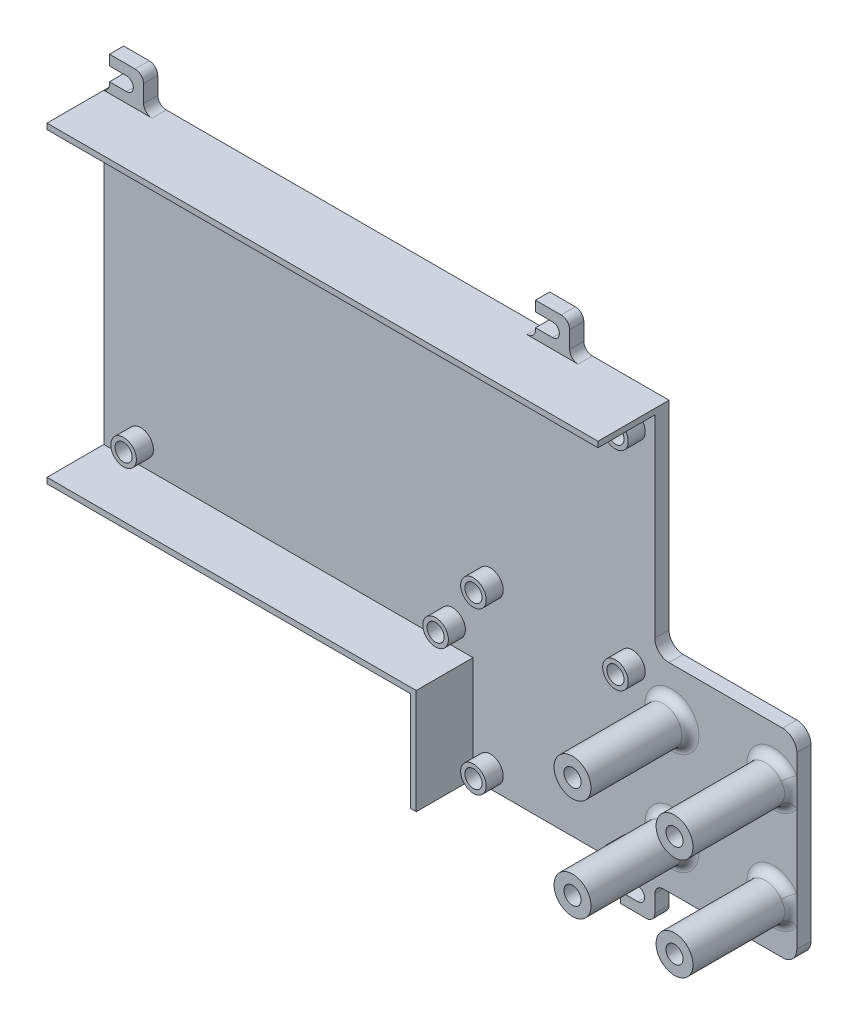
SolidWorks part; units mm, degrees
material "ABS"
ref_plane "X-Y Datum" through (0, 0, 0) normal (0, 0, 1) x (1, 0, 0)
ref_plane "X-Z Datum" through (0, 0, 0) normal (0, 1, 0) x (1, 0, 0)
ref_plane "Y-Z Datum" through (0, 0, 0) normal (1, 0, 0) x (0, 0, -1)
sketch "Sketch1" plane through (0, 0, 0) normal (0, 0, 1) x (1, 0, 0)
  line L1 (-167.3248, 270.3744) -> (-39.3248, 270.3744)
  line L2 (-167.3248, 270.3744) -> (-167.3248, 160.3744)
  line L3 (-167.3248, 160.3744) -> (-39.3248, 160.3744)
  line L4 (-39.3248, 270.3744) -> (-39.3248, 160.3744)
  line L5 (-39.3248, 270.3744) -> (26.6752, 270.3744)
  line L6 (-39.3248, 270.3744) -> (-39.3248, 125.3744)
  line L7 (-39.3248, 125.3744) -> (26.6752, 125.3744)
  line L8 (26.6752, 270.3744) -> (26.6752, 125.3744)
  line L9 (26.6752, 125.3744) -> (76.6752, 125.3744)
  line L10 (26.6752, 125.3744) -> (26.6752, 195.3744)
  line L11 (26.6752, 195.3744) -> (76.6752, 195.3744)
  line L12 (76.6752, 125.3744) -> (76.6752, 195.3744)
  dimension "D1" = 110
  dimension "D2" = 128
  dimension "D3" = 66
  dimension "D4" = 145
  dimension "D5" = 50
  dimension "D6" = 70
extrude "Boss-Extrude1" add sketch "Sketch1" along normal blind 5 contours L4 L1 L2 L3 | L8 L5 L4 L6 L7 | L9 L12 L11 L8 region at (-103.3248, 215.3744, 0) region at (-6.3248, 197.8744, 0) region at (51.6752, 160.3744, 0)
sketch "Sketch2" plane through (0, 0, 5) normal (0, 0, 1) x (1, 0, 0)
  circle A0 centre (-44.4998, 262.4914) radius 3.025
  circle A1 centre (-154.3548, 262.4914) radius 3.025
  circle A2 centre (-154.3548, 262.4914) radius 4.5
  circle A3 centre (-44.4998, 262.4914) radius 4.5
  circle A4 centre (-44.4998, 169.5274) radius 3.025
  circle A5 centre (-44.4998, 169.5274) radius 4.5
  circle A6 centre (-154.3548, 169.5274) radius 4.5
  circle A7 centre (-154.3548, 169.5274) radius 3.025
  circle A8 centre (-31.1818, 131.5554) radius 4.5
  circle A9 centre (-31.1818, 131.5554) radius 3.025
  circle A10 centre (18.8182, 131.5554) radius 3.025
  circle A11 centre (18.8182, 131.5554) radius 4.5
  circle A12 centre (18.8182, 188.3054) radius 3.025
  circle A13 centre (18.8182, 188.3054) radius 4.5
  circle A14 centre (-31.1818, 188.3054) radius 4.5
  circle A15 centre (-31.1818, 188.3054) radius 3.025
  circle A16 centre (-31.1818, 261.5554) radius 3.025
  circle A17 centre (-31.1818, 261.5554) radius 4.5
  circle A18 centre (18.8182, 261.5554) radius 4.5
  circle A19 centre (18.8182, 261.5554) radius 3.025
  point P0 (-154.3548, 262.4914)
  point P1 (-44.4998, 262.4914)
  point P3 (-44.4998, 169.5274)
  point P5 (-154.3548, 169.5274)
  point P7 (18.8182, 261.5554)
  point P9 (-31.1818, 261.5554)
  point P11 (-31.1818, 188.3054)
  point P13 (-31.1818, 131.5554)
  point P15 (18.8182, 131.5554)
  point P17 (18.8182, 188.3054)
  dimension "D1" = 6.05
  dimension "D2" = 9
extrude "Boss-Extrude2" add sketch "Sketch2" along normal blind 6
sketch "Sketch3" plane through (0, 0, 5) normal (0, 0, 1) x (1, 0, 0)
  line L0 (26.6752, 270.3744) -> (26.6752, 195.3744) construction
  line L1 (-167.3248, 270.3744) -> (26.6752, 270.3744)
  line L2 (-167.3248, 270.3744) -> (-167.3248, 268.3744)
  line L3 (-167.3248, 268.3744) -> (26.6752, 268.3744)
  line L4 (26.6752, 270.3744) -> (26.6752, 268.3744)
  line L6 (-167.3248, 160.3744) -> (-39.3248, 160.3744)
  line L7 (-167.3248, 160.3744) -> (-167.3248, 162.3744)
  line L8 (-167.3248, 162.3744) -> (-39.3248, 162.3744)
  line L9 (-39.3248, 160.3744) -> (-39.3248, 162.3744)
  line L10 (-39.3248, 125.3744) -> (-37.3248, 125.3744)
  line L11 (-39.3248, 125.3744) -> (-39.3248, 162.3744)
  line L12 (-39.3248, 162.3744) -> (-37.3248, 162.3744)
  line L13 (-37.3248, 125.3744) -> (-37.3248, 162.3744)
  line M14 (-167.3248, 160.3744) -> (-39.3248, 160.3744)
  line M15 (-39.3248, 160.3744) -> (-39.3248, 125.3744)
  line M16 (-39.3248, 125.3744) -> (76.6752, 125.3744)
  line M19 (26.6752, 195.3744) -> (26.6752, 270.3744)
  line M20 (26.6752, 270.3744) -> (-167.3248, 270.3744)
  line M21 (-167.3248, 270.3744) -> (-167.3248, 160.3744)
  dimension "D1" = 2
  dimension "D2" = 2
  dimension "D3" = 2
extrude "Boss-Extrude3" add sketch "Sketch3" along normal blind 20 contours L13 L12 L9 M16 M15 | L9 L8 M14 M21 | L3 M21 M19 M20 region at (-103.3248, 161.3744, 5) region at (-70.3248, 269.3744, 5) region at (-38.3248, 143.8744, 5)
sketch "Sketch5" plane through (0, 0, 5) normal (0, 0, 1) x (1, 0, 0)
  circle A0 centre (32.6993, 178.3575) radius 3.025
  circle A1 centre (68.6203, 178.3575) radius 3.025
  circle A2 centre (68.6203, 142.4365) radius 3.025
  circle A3 centre (32.6993, 142.4365) radius 3.025
  circle A4 centre (68.6203, 178.3575) radius 6.5
  circle A5 centre (32.6993, 178.3575) radius 6.5
  circle A6 centre (32.6993, 142.4365) radius 6.5
  circle A7 centre (68.6203, 142.4365) radius 6.5
  point P1 (32.6993, 178.3575)
  point P3 (32.6993, 142.4365)
  dimension "D1" = 6.05
  dimension "D2" = 13
extrude "Boss-Extrude4" add sketch "Sketch5" along normal blind 35
fillet "Fillet1" radius 3 4 edges at (39.1993, 178.3575, 5) (75.1203, 178.3575, 5) (75.1203, 142.4365, 5) (39.1993, 142.4365, 5)
sketch "Sketch6" plane through (0, 0, 0) normal (0, 0, -1) x (-1, 0, 0)
  line L0 (167.3248, 160.3744) -> (39.3248, 160.3744) construction
  line L1 (102.3248, 160.3744) -> (90.3248, 160.3744)
  line L2 (102.3248, 160.3744) -> (102.3248, 148.3744)
  line L3 (102.3248, 148.3744) -> (90.3248, 148.3744)
  line L4 (90.3248, 160.3744) -> (90.3248, 148.3744)
  line L5 (-26.6752, 270.3744) -> (167.3248, 270.3744) construction
  line L6 (165.3248, 270.3744) -> (153.3248, 270.3744)
  line L7 (165.3248, 270.3744) -> (165.3248, 282.3744)
  line L8 (165.3248, 282.3744) -> (153.3248, 282.3744)
  line L9 (153.3248, 270.3744) -> (153.3248, 282.3744)
  line L10 (37.3248, 125.3744) -> (-76.6752, 125.3744) construction
  line L11 (-14.6752, 125.3744) -> (-26.6752, 125.3744)
  line L12 (-14.6752, 125.3744) -> (-14.6752, 113.3744)
  line L13 (-14.6752, 113.3744) -> (-26.6752, 113.3744)
  line L14 (-26.6752, 125.3744) -> (-26.6752, 113.3744)
  line L15 (96.3248, 160.3744) -> (96.3248, 148.3744) construction
  line L16 (15.3248, 270.3744) -> (3.3248, 270.3744)
  line L17 (15.3248, 270.3744) -> (15.3248, 282.3744)
  line L18 (15.3248, 282.3744) -> (3.3248, 282.3744)
  line L19 (3.3248, 270.3744) -> (3.3248, 282.3744)
  line L20 (167.3248, 162.3744) -> (167.3248, 160.3744) construction
  line L21 (159.3248, 282.3744) -> (159.3248, 270.3744) construction
  line L22 (9.3248, 282.3744) -> (9.3248, 270.3744) construction
  line L23 (-20.6752, 125.3744) -> (-20.6752, 113.3744) construction
  line L24 (167.3248, 268.3744) -> (167.3248, 162.3744) construction
  line L27 (-26.6752, 268.3744) -> (-26.6752, 195.3744) construction
  line L28 (-76.6752, 125.3744) -> (-76.6752, 137.3997) construction
  circle A0 centre (96.3248, 154.3744) radius 2 construction
  circle A1 centre (-20.6752, 119.3744) radius 2 construction
  circle A2 centre (9.3248, 276.3744) radius 2 construction
  circle A3 centre (159.3248, 276.3744) radius 2 construction
  dimension "D1" = 4
  dimension "D2" = 12
  dimension "D3" = 12
  dimension "D4" = 65
  dimension "D5" = 2
  dimension "D6" = 30
  dimension "D7" = 50
extrude "Boss-Extrude5" add sketch "Sketch6" against normal blind 5
hole_wizard "M4 Clearance Hole1" positions "Sketch9" profile "Sketch8" hole size "M4" standard "ANSI Metric" end condition through all
sketch "Sketch9" plane through (0, 0, 5) normal (0, 0, 1) x (1, 0, 0)
  line L0 (-96.3248, 160.3744) -> (-96.3248, 148.3744) construction
  point P0 (-96.3248, 154.3744)
  point P4 (-159.3248, 276.3744)
  point P7 (-9.3248, 276.3744)
  point P10 (20.6752, 119.3744)
sketch "Sketch8" plane through (-96.3248, 154.3744, 5) normal (1, 0, 0) x (0, -1, 0)
  line L0 (0, 0) -> (0, 5)
  line L1 (0, 5) -> (2.4, 5)
  line L2 (2.4, 5) -> (2.4, 0)
  line L5 (2.4, 0) -> (0, 0)
  line L11 (0, -6.35) -> (0, 107.95) construction
  dimension "Thru Hole Dia." = 4.8
  dimension "Thru Hole Depth" = 5
sketch "Sketch10" plane through (0, 0, 5) normal (0, 0, 1) x (1, 0, 0)
  line L0 (-159.3248, 278.7744) -> (-165.3248, 278.7744)
  line L1 (-159.3248, 282.3744) -> (-159.3248, 270.3744) construction
  line L2 (-165.3248, 270.3744) -> (-165.3248, 282.3744) construction
  line L3 (-159.3248, 273.9744) -> (-165.3248, 273.9744)
  line L4 (-96.3248, 156.7744) -> (-102.3248, 156.7744)
  line L5 (-96.3248, 160.3744) -> (-96.3248, 148.3744) construction
  line L6 (-102.3248, 160.3744) -> (-102.3248, 148.3744) construction
  line L7 (-96.3248, 151.9744) -> (-102.3248, 151.9744)
  line L8 (20.6752, 121.7744) -> (14.6752, 121.7744)
  line L9 (20.6752, 125.3744) -> (20.6752, 113.3744) construction
  line L10 (14.6752, 125.3744) -> (14.6752, 113.3744) construction
  line L11 (20.6752, 116.9744) -> (14.6752, 116.9744)
  line L12 (-9.3248, 278.7744) -> (-15.3248, 278.7744)
  line L13 (-9.3248, 282.3744) -> (-9.3248, 270.3744) construction
  line L14 (-15.3248, 270.3744) -> (-15.3248, 282.3744) construction
  line L15 (-9.3248, 273.9744) -> (-15.3248, 273.9744)
  line L20 (-102.3248, 160.3744) -> (-102.3248, 148.3744)
  line L21 (-102.3248, 148.3744) -> (-90.3248, 148.3744)
  line L22 (-90.3248, 148.3744) -> (-90.3248, 160.3744)
  line L23 (-90.3248, 160.3744) -> (-102.3248, 160.3744)
  line L24 (-102.3248, 160.3744) -> (-102.3248, 148.3744)
  line L25 (-102.3248, 148.3744) -> (-90.3248, 148.3744)
  line L26 (-90.3248, 148.3744) -> (-90.3248, 160.3744)
  line L27 (-90.3248, 160.3744) -> (-102.3248, 160.3744)
  line L28 (-15.3248, 282.3744) -> (-15.3248, 270.3744)
  line L29 (-15.3248, 270.3744) -> (-3.3248, 270.3744)
  line L30 (76.6752, 147.4732) -> (76.6752, 173.3208)
  line L31 (76.6752, 183.3942) -> (76.6752, 195.3744)
  line L32 (76.6752, 195.3744) -> (26.6752, 195.3744)
  line L33 (26.6752, 195.3744) -> (26.6752, 268.3744)
  line L34 (26.6752, 268.3744) -> (-167.3248, 268.3744)
  line L35 (-167.3248, 268.3744) -> (-167.3248, 162.3744)
  line L36 (-167.3248, 162.3744) -> (-37.3248, 162.3744)
  line L37 (-37.3248, 162.3744) -> (-37.3248, 125.3744)
  line L38 (-37.3248, 125.3744) -> (14.6752, 125.3744)
  line L39 (14.6752, 125.3744) -> (14.6752, 113.3744)
  line L40 (14.6752, 113.3744) -> (26.6752, 113.3744)
  line L41 (26.6752, 113.3744) -> (26.6752, 125.3744)
  line L44 (76.6752, 147.4732) -> (76.6752, 173.3208)
  line L45 (76.6752, 183.3942) -> (76.6752, 195.3744)
  line L46 (76.6752, 195.3744) -> (26.6752, 195.3744)
  line L47 (26.6752, 195.3744) -> (26.6752, 268.3744)
  line L48 (26.6752, 268.3744) -> (-167.3248, 268.3744)
  line L49 (-167.3248, 268.3744) -> (-167.3248, 162.3744)
  line L50 (-167.3248, 162.3744) -> (-37.3248, 162.3744)
  line L51 (-37.3248, 162.3744) -> (-37.3248, 125.3744)
  line L52 (-37.3248, 125.3744) -> (14.6752, 125.3744)
  line L53 (14.6752, 125.3744) -> (14.6752, 113.3744)
  line L54 (14.6752, 113.3744) -> (26.6752, 113.3744)
  line L55 (26.6752, 113.3744) -> (26.6752, 125.3744)
  line L58 (-3.3248, 270.3744) -> (-3.3248, 282.3744)
  line L59 (-3.3248, 282.3744) -> (-15.3248, 282.3744)
  line L60 (-15.3248, 282.3744) -> (-15.3248, 270.3744)
  line L61 (-15.3248, 270.3744) -> (-3.3248, 270.3744)
  line L62 (-3.3248, 270.3744) -> (-3.3248, 282.3744)
  line L63 (-3.3248, 282.3744) -> (-15.3248, 282.3744)
  line L64 (-165.3248, 282.3744) -> (-165.3248, 270.3744)
  line L65 (-165.3248, 270.3744) -> (-153.3248, 270.3744)
  line L66 (-153.3248, 270.3744) -> (-153.3248, 282.3744)
  line L67 (-153.3248, 282.3744) -> (-165.3248, 282.3744)
  line L68 (-165.3248, 282.3744) -> (-165.3248, 270.3744)
  line L69 (-165.3248, 270.3744) -> (-153.3248, 270.3744)
  line L70 (-153.3248, 270.3744) -> (-153.3248, 282.3744)
  line L71 (-153.3248, 282.3744) -> (-165.3248, 282.3744)
  line L80 (26.6752, 125.3744) -> (76.6752, 125.3744)
  line L81 (26.6752, 125.3744) -> (76.6752, 125.3744)
  line L82 (76.6752, 125.3744) -> (76.6752, 137.3997)
  line L83 (76.6752, 125.3744) -> (76.6752, 137.3997)
  circle A0 centre (-159.3248, 276.3744) radius 2.4 construction
  circle A1 centre (-96.3248, 154.3744) radius 2.4 construction
  circle A2 centre (20.6752, 119.3744) radius 2.4 construction
  circle A3 centre (-9.3248, 276.3744) radius 2.4 construction
  circle A4 centre (-159.3248, 276.3744) radius 2.4
  circle A5 centre (-9.3248, 276.3744) radius 2.4
  arc A6 (76.6752, 183.3942) -> (76.6752, 173.3208) centre (68.6203, 178.3575) ccw
  arc A7 (76.6752, 147.4732) -> (76.6752, 137.3997) centre (68.6203, 142.4365) ccw
  arc A8 (76.6752, 183.3942) -> (76.6752, 173.3208) centre (68.6203, 178.3575) ccw
  arc A9 (76.6752, 147.4732) -> (76.6752, 137.3997) centre (68.6203, 142.4365) ccw
  circle A10 centre (20.6752, 119.3744) radius 2.4
  circle A11 centre (-96.3248, 154.3744) radius 2.4
  circle M29 centre (-96.3248, 154.3744) radius 2.4
  line M30 (-102.3248, 160.3744) -> (-102.3248, 148.3744)
  dimension "D1" = 0
  dimension "D2" = 0
  dimension "D3" = 0
  dimension "D4" = 0
extrude "Cut-Extrude1" cut sketch "Sketch10" against normal through all contours L7 L4 M29 M30 | A4 L0 L68 L3 | A5 L12 L60 L15 | A10 L8 L53 L11 region at (-163.2324, 276.3744, 5) region at (-100.2324, 154.3744, 5) region at (16.7676, 119.3744, 5) region at (-13.2324, 276.3744, 5)
fillet "Fillet2" radius 3 12 edges at (-153.3248, 282.3744, 2.5) (-153.3248, 270.3744, 2.5) (-165.3248, 270.3744, 2.5) (-15.3248, 270.3744, 2.5) (-3.3248, 270.3744, 2.5) (-3.3248, 282.3744, 2.5) (-90.3248, 148.3744, 2.5) (26.6752, 113.3744, 2.5) (26.6752, 125.3744, 2.5) (14.6752, 125.3744, 2.5) (-102.3248, 160.3744, 2.5) (-90.3248, 160.3744, 2.5)
fillet "Fillet3" radius 5 3 edges at (26.6752, 195.3744, 2.5) (76.6752, 195.3744, 2.5) (76.6752, 125.3744, 2.5)
equation "\"16mmm\"=20"
